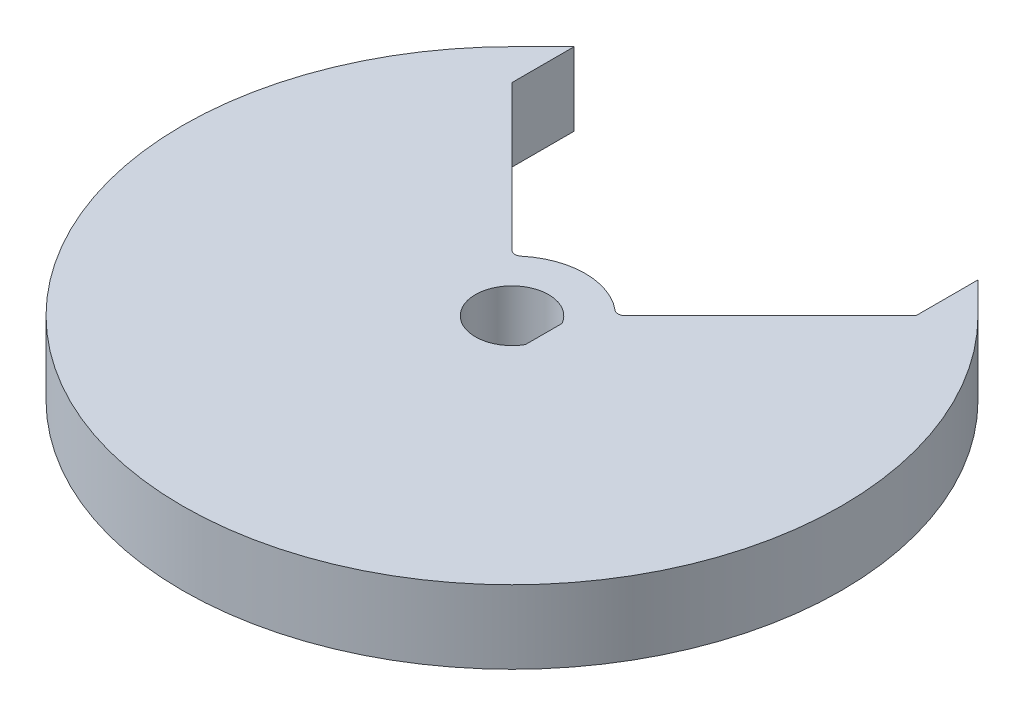
SolidWorks part; units mm, degrees
material "ABS"
ref_plane "Front Plane" through (0, 0, 0) normal (0, 0, 1) x (1, 0, 0)
ref_plane "Top Plane" through (0, 0, 0) normal (0, 1, 0) x (1, 0, 0)
ref_plane "Right Plane" through (0, 0, 0) normal (1, 0, 0) x (0, 0, -1)
sketch "Sketch1" plane through (0, 0, 0) normal (0, 1, 0) x (1, 0, 0)
  line L0 (-31.8198, 31.8198) -> (-7.0711, 7.0711)
  line L1 (7.0711, 7.0711) -> (31.8198, 31.8198)
  line L2 (0, 0) -> (0, 20) construction
  line L3 (0, 0) -> (-7.0711, 7.0711) construction
  line L4 (7.0711, 7.0711) -> (0, 0) construction
  arc A0 (-31.8198, 31.8198) -> (31.8198, 31.8198) centre (0, 0) ccw
  circle A1 centre (0, 0) radius 5
  arc A2 (7.0711, 7.0711) -> (-7.0711, 7.0711) centre (0, 0) ccw
  dimension "D1" = 10
  dimension "D2" = 90
  dimension "D3" = 20
  dimension "D4" = 45
extrude "Boss-Extrude1" add sketch "Sketch1" along normal blind 10
fillet "Fillet1" radius 1 2 edges at (7.0711, 5, -7.0711) (-7.0711, 5, -7.0711)
sketch "Sketch2" plane through (0, 10, 0) normal (0, 1, 0) x (1, 0, 0)
  line L0 (4.3301, 2.5) -> (4.3301, -2.5)
  arc A0 (4.3301, -2.5) -> (4.3301, 2.5) centre (0, 0) ccw
  circle A1 centre (0, 0) radius 5 construction
  dimension "D1" = 5
extrude "Shaft D" add sketch "Sketch2" against normal up to surface (10 mm away) up to face at (0, 0, -3.2457)
sketch "Sketch3" plane through (0, 10, 0) normal (0, 1, 0) x (1, 0, 0)
  line L0 (-31.8198, 31.8198) -> (-27.5772, 36.0624)
  line L1 (-27.5772, 36.0624) -> (-27.5772, 27.5772)
  line L2 (-7.746, 7.746) -> (-31.8198, 31.8198) construction
  line L3 (-27.5772, 27.5772) -> (-31.8198, 31.8198)
  line L4 (0, 0) -> (0, 30.6174) construction
  line L5 (27.5772, 27.5772) -> (31.8198, 31.8198)
  line L6 (27.5772, 36.0624) -> (27.5772, 27.5772)
  line L7 (31.8198, 31.8198) -> (27.5772, 36.0624)
  point P9 (-27.3942, 27.3942)
  dimension "D1" = 6
extrude "Boss-Extrude2" add sketch "Sketch3" against normal up to surface (10 mm away) up to face at (0, 0, -3.2457)
